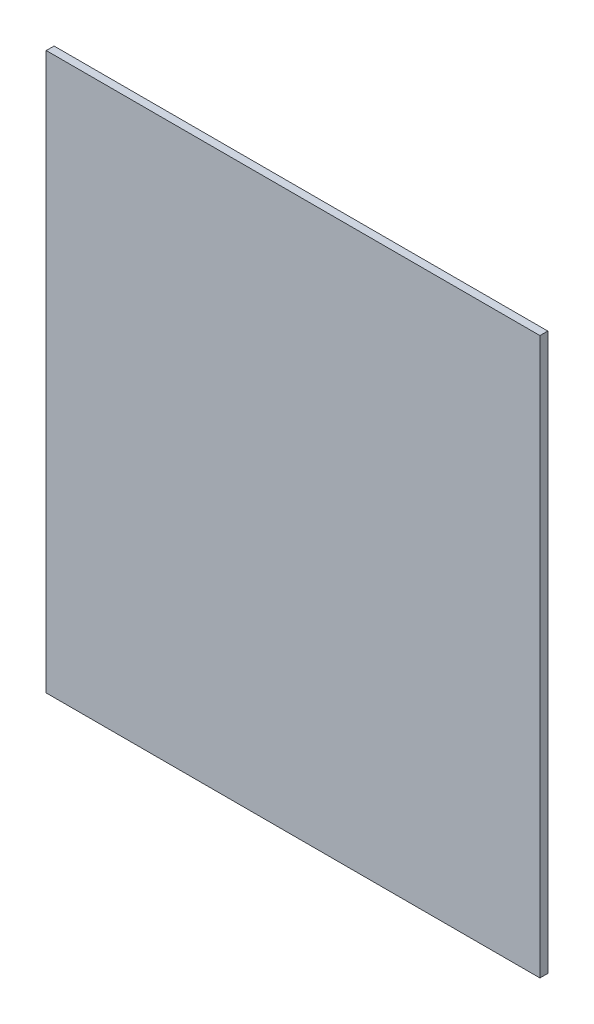
SolidWorks part; units mm, degrees
ref_plane "Front Plane" through (0, 0, 0) normal (0, 0, 1) x (1, 0, 0)
ref_plane "Top Plane" through (0, 0, 0) normal (0, 1, 0) x (1, 0, 0)
ref_plane "Right Plane" through (0, 0, 0) normal (1, 0, 0) x (0, 0, -1)
sketch "Sketch1" plane through (0, 0, 0) normal (0, 0, 1) x (1, 0, 0)
  line L1 (-200.025, 225.425) -> (200.025, 225.425)
  line L2 (-200.025, 225.425) -> (-200.025, -225.425)
  line L3 (-200.025, -225.425) -> (200.025, -225.425)
  line L4 (200.025, 225.425) -> (200.025, -225.425)
  point P5 (0, -225.425)
  point P7 (-200.025, 0)
  dimension "D1" = 400.05
  dimension "D2" = 450.85
extrude "Boss-Extrude1" add sketch "Sketch1" along normal blind 6.35
